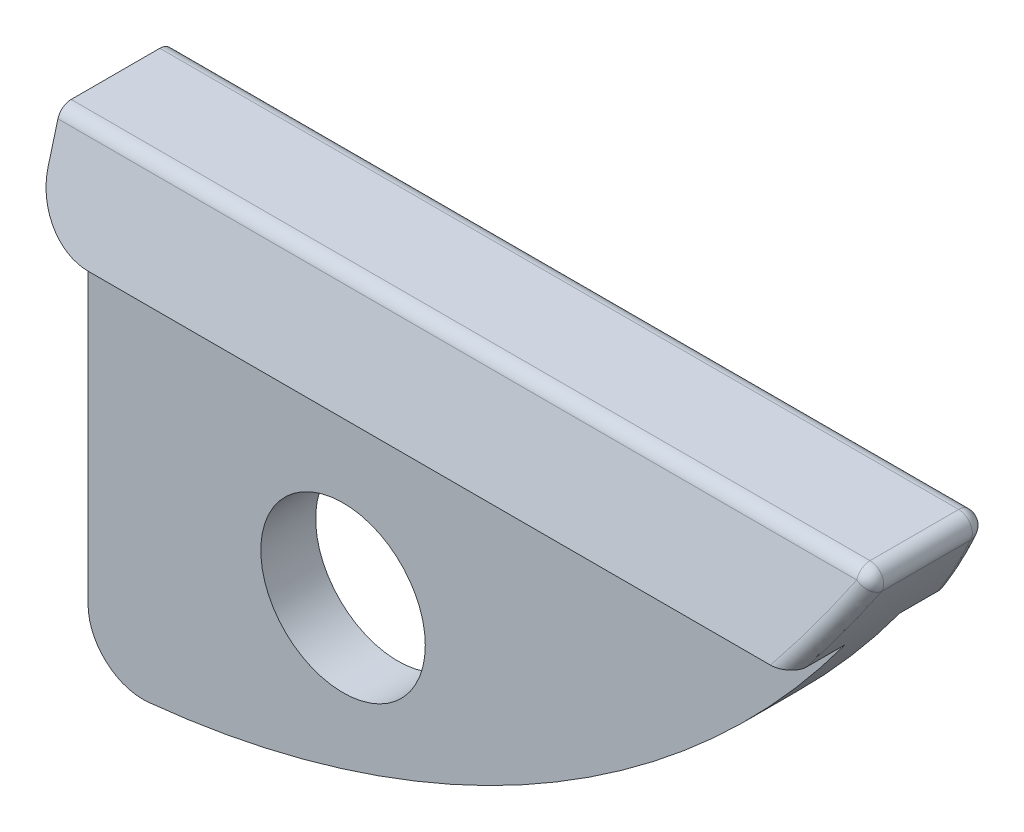
SolidWorks part; units mm, degrees
ref_plane "Piano frontale" through (0, 0, 0) normal (0, 0, 1) x (1, 0, 0)
ref_plane "Piano superiore" through (0, 0, 0) normal (0, 1, 0) x (1, 0, 0)
ref_plane "Piano destro" through (0, 0, 0) normal (1, 0, 0) x (0, 0, -1)
sketch "Schizzo1" plane through (0, 0, 0) normal (0, 0, 1) x (1, 0, 0)
  line L1 (-84.4168, 25.3125) -> (-54.4168, 25.3125)
  line L2 (-84.4168, 25.3125) -> (-84.4168, 6.9125)
  line L3 (-84.4168, 6.9125) -> (-54.4168, 6.9125)
  line L4 (-54.4168, 25.3125) -> (-54.4168, 6.9125)
  circle A0 centre (-75.1168, 13.9125) radius 3
  dimension "D5" = 6
  dimension "D1" = 18.4
  dimension "D2" = 30
  dimension "D3" = 9.3
  dimension "D4" = 11.4
extrude "Estrusione-Estrusione1" add sketch "Schizzo1" along normal mid plane 2
ref_plane "Piano1" through (-84.4168, 0, 0) normal (-1, 0, 0) x (0, 0, 1)
sketch "Schizzo2" plane through (-84.4168, 0, 0) normal (-1, 0, 0) x (0, 0, 1)
  line L2 (3, 21.5804) -> (-3, 21.5804)
  line L4 (0, 26.1621) -> (0, 21.5804) construction
  line L6 (-2, 25.3125) -> (2, 25.3125)
  line L8 (1, 25.3125) -> (-1, 25.3125) construction
  line L9 (2, 25.3125) -> (3, 21.5804)
  line L10 (-2, 25.3125) -> (-3, 21.5804)
  point P7 (0, 25.3125)
  dimension "D1" = 2
  dimension "D2" = 75
  dimension "D3" = 3
extrude "Estrusione-Estrusione2" add sketch "Schizzo2" against normal through all
sketch "Schizzo4" plane through (0, 0, 0) normal (0, 0, 1) x (1, 0, 0)
  line L0 (-54.4168, 25.3125) -> (-54.4168, 6.9125)
  line L1 (-54.4168, 6.9125) -> (-84.4168, 6.9125)
  arc A0 (-84.4168, 6.9125) -> (-54.4168, 25.3125) centre (-85.777, 42.7867) ccw
extrude "Taglio-Estrusione1" cut sketch "Schizzo4" against normal mid plane 7
fillet "Raccordo1" radius 2 1 edges at (-84.4168, 21.5804, 2) type face fillet first side face at (-70.6133, 21.5804, 2) second side face at (-84.4168, 18.8465, 0)
fillet "Raccordo2" radius 2 1 edges at (-84.4168, 21.5804, -2) type face fillet first side face at (-70.6133, 21.5804, -2) second side face at (-84.4168, 19.3465, -0.067)
fillet "Raccordo3" radius 2 1 edges at (-84.4168, 6.9125, 0) type face fillet first side face at (-84.4168, 19.8465, 0) second side face at (-62.6787, 18.0465, 0)
fillet "Raccordo4" radius 0.5 5 edges at (-69.4168, 25.3125, 2) (-54.4168, 25.3125, 0) (-55.5556, 23.4095, 2.5099) (-55.5556, 23.4095, -2.5099) (-69.4168, 25.3125, -2)
